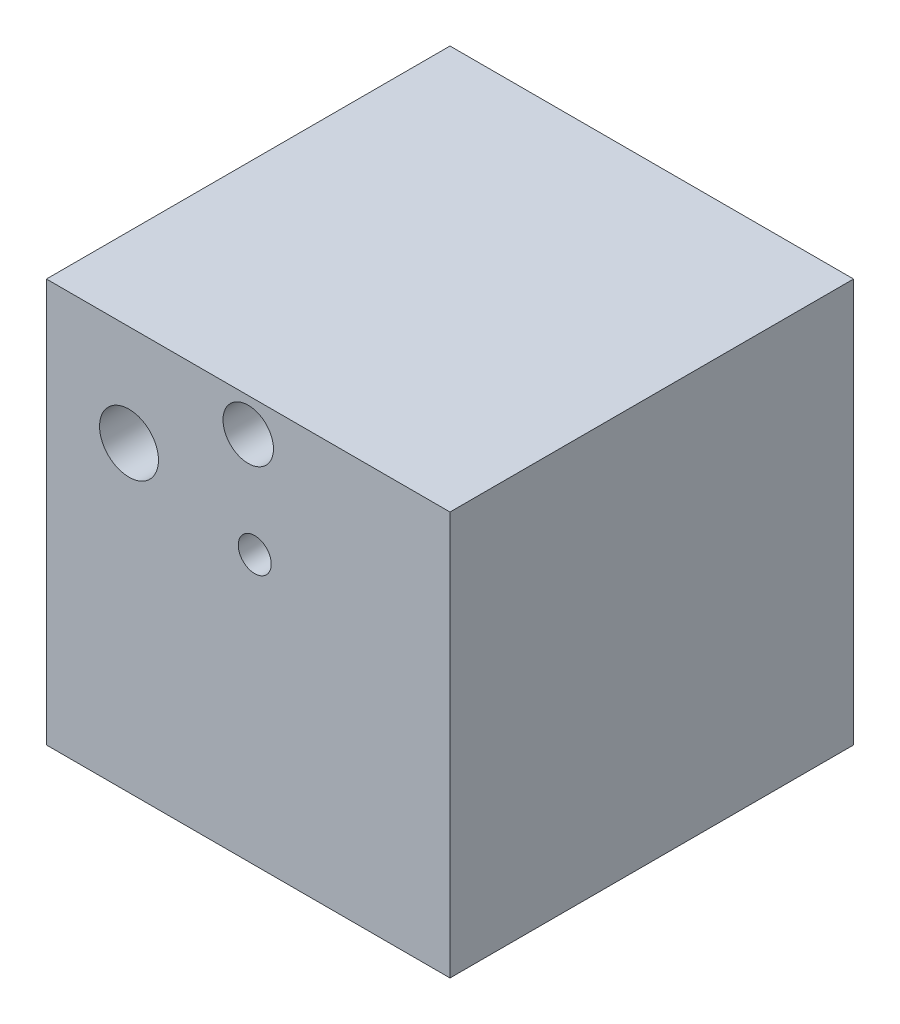
SolidWorks part; units mm, degrees
ref_plane "Front Plane" through (0, 0, 0) normal (0, 0, 1) x (1, 0, 0)
ref_plane "Top Plane" through (0, 0, 0) normal (0, 1, 0) x (1, 0, 0)
ref_plane "Right Plane" through (0, 0, 0) normal (1, 0, 0) x (0, 0, -1)
sketch "Sketch2" plane through (0, 0, 0) normal (0, 1, 0) x (1, 0, 0)
  line L1 (-38.1, -38.1) -> (38.1, -38.1)
  line L2 (-38.1, -38.1) -> (-38.1, 38.1)
  line L3 (-38.1, 38.1) -> (38.1, 38.1)
  line L4 (38.1, -38.1) -> (38.1, 38.1)
  line L5 (-38.1, -38.1) -> (38.1, 38.1) construction
  line L6 (-38.1, 38.1) -> (38.1, -38.1) construction
  point P0 (0, 0)
  dimension "D1" = 76.2
  dimension "D2" = 76.2
extrude "Boss-Extrude1" add sketch "Sketch2" along normal blind 76.2
sketch "Sketch3" plane through (0, 0, 38.1) normal (0, 0, 1) x (1, 0, 0)
  line L0 (-38.1, 76.2) -> (38.1, 76.2) construction
  line L1 (-38.1, 0) -> (38.1, 0) construction
  circle A0 centre (0, 69.85) radius 4.7625
  circle A1 centre (-22.5088, 57.15) radius 5.5626
  circle A2 centre (1.2311, 50.8) radius 3.1153
  point P9 (0, 0)
  dimension "D1" = 9.525
  dimension "D3" = 25.8445
  dimension "D4" = 11.1252
  dimension "D6" = 24.5745
  dimension "D7" = 25.4
  dimension "D2" = 6.35
  dimension "D5" = 19.05
extrude "Cut-Extrude1" cut sketch "Sketch3" against normal blind 63.5
equation "\"D1@Sketch2\"=\"D2@Sketch2\""
equation "\"D1@Boss-Extrude1\"=\"D2@Sketch2\""
